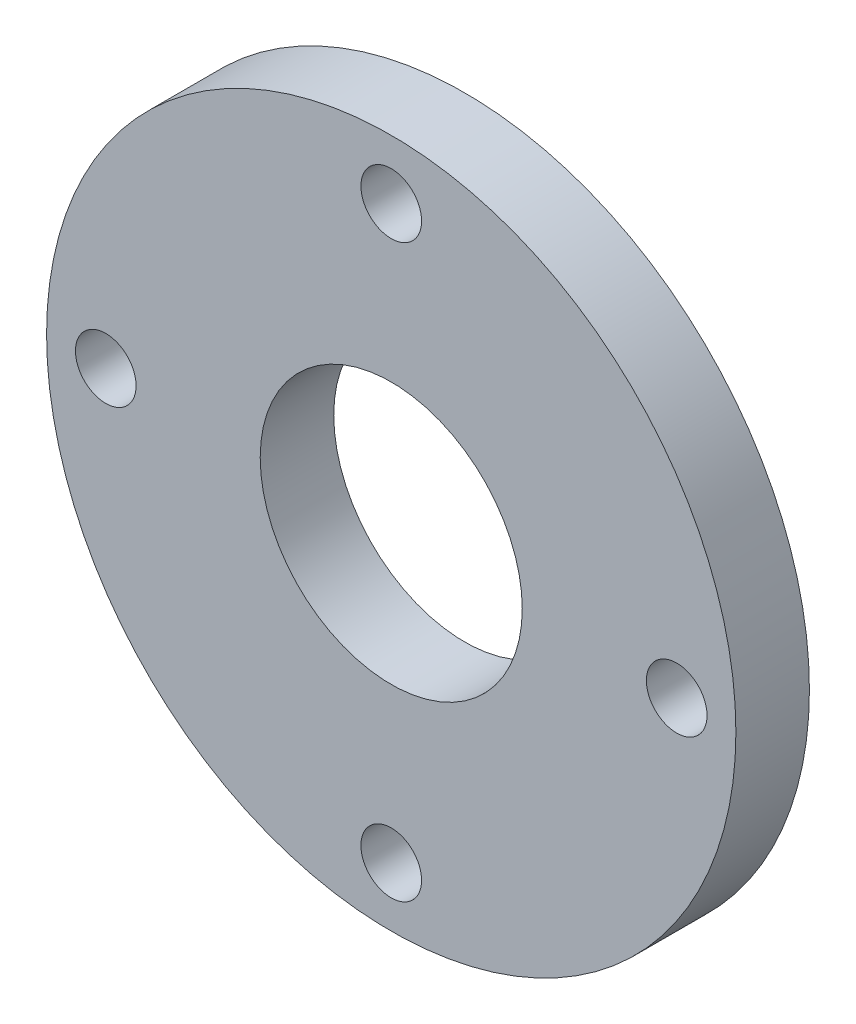
SolidWorks part; units mm, degrees
ref_plane "Front Plane" through (0, 0, 0) normal (0, 0, 1) x (1, 0, 0)
ref_plane "Top Plane" through (0, 0, 0) normal (0, 1, 0) x (1, 0, 0)
ref_plane "Right Plane" through (0, 0, 0) normal (1, 0, 0) x (0, 0, -1)
sketch "Sketch1" plane through (0, 0, 0) normal (1, 0, 0) x (0, 0, -1)
  line L0 (-108, -9.5) -> (-149, -9.5)
  line L5 (-1000, 0) -> (49000, 0)
  line L6 (0, -9.5) -> (0, 9.5)
  line L13 (0, 9.5) -> (-46.4, 9.5)
  line L26 (-46.4, 9.5) -> (-46.4, 14)
  line L27 (-46.4, 14) -> (-108, 14)
  line L32 (-108, 14) -> (-108, 9.5)
  line L34 (-165, 7) -> (-165, -7)
  line L36 (-108, -9.5) -> (-108, -14)
  line L37 (-108, -14) -> (-46.4, -14)
  line L38 (-46.4, -14) -> (-46.4, -9.5)
  line L39 (0, -9.5) -> (-46.4, -9.5)
  line L40 (-22.625, 37.5) -> (-14.625, 37.5)
  line L41 (-124.6, 22.6187) -> (-108, 22.6187)
  line L42 (-124.6, 22.6187) -> (-124.6, -22.6187)
  line L43 (-124.6, -22.6187) -> (-108, -22.6187)
  line L44 (-108, 22.6187) -> (-108, -22.6187)
  line L45 (-124.6, 22.6187) -> (-108, -22.6187) construction
  line L46 (-124.6, -22.6187) -> (-108, 22.6187) construction
  line L47 (-29.8, 22.6187) -> (-46.4, 22.6187)
  line L48 (-29.8, 22.6187) -> (-29.8, -22.6187)
  line L49 (-29.8, -22.6187) -> (-46.4, -22.6187)
  line L50 (-46.4, 22.6187) -> (-46.4, -22.6187)
  line L51 (-29.8, 22.6187) -> (-46.4, -22.6187) construction
  line L52 (-29.8, -22.6187) -> (-46.4, 22.6187) construction
  line L59 (-14.625, 37.5) -> (-14.625, -37.5)
  line L60 (-14.625, -37.5) -> (-22.625, -37.5)
  line L61 (-22.625, -22.6187) -> (-26.625, -22.6187)
  line L62 (-26.625, -22.6187) -> (-26.625, -12.5)
  line L63 (-26.625, -12.5) -> (-22.625, -12.5)
  line L64 (-22.625, -12.5) -> (-22.625, 12.5)
  line L65 (-22.625, 12.5) -> (-26.625, 12.5)
  line L66 (-26.625, 12.5) -> (-26.625, 22.6187)
  line L67 (-26.625, 22.6187) -> (-22.625, 22.6187)
  line L68 (-22.625, 22.6187) -> (-22.625, 37.5)
  line L69 (-22.625, -22.6187) -> (-22.625, -37.5)
  line L71 (-136.284, 37.5) -> (-23.625, 37.5)
  line L72 (-136.284, 37.5) -> (-136.284, -37.5)
  line L73 (-136.284, -37.5) -> (-23.625, -37.5)
  line L74 (-23.625, 37.5) -> (-23.625, -37.5)
  line L75 (-136.284, 37.5) -> (-23.625, -37.5) construction
  line L76 (-136.284, -37.5) -> (-23.625, 37.5) construction
  line L77 (-149, -9.5) -> (-149, -7)
  line L78 (-149, -7) -> (-165, -7)
  line L79 (-108, 9.5) -> (-149, 9.5)
  line L80 (-149, 7) -> (-165, 7)
  line L81 (-149, 9.5) -> (-149, 7)
  line L82 (-128.5, 9.5) -> (-128.5, -9.5) construction
  line L83 (-23.2, 9.5) -> (-23.2, -9.5) construction
  line L96 (-136.284, 37.5) -> (-144.284, 37.5)
  line L98 (-136.284, -37.5) -> (-144.284, -37.5)
  line L99 (-144.284, 37.5) -> (-144.284, -37.5)
  line L110 (-136.284, 37.5) -> (-136.284, -37.5)
  point P3 (0, 0)
  point P18 (-116.3, 0)
  point P24 (-38.1, 0)
  point P29 (-79.9545, 0)
  point P48 (-14.625, 31.0593)
  point P70 (-144.284, 31.0593)
revolve "Main_body" add sketch "Sketch1" angle 360 about L5 region at (0, 23.5, 140.284)
sketch "Sketch5" plane through (0, 0, 144.284) normal (0, 0, 1) x (1, 0, 0)
  circle A0 centre (0, 0) radius 14.2558
  dimension "D1" = 28.5115
extrude "seal_seat" cut sketch "Sketch5" against normal through all
hole_wizard "M6 Clearance Hole1" positions "Sketch3" profile "Sketch4" hole size "M6" standard "ANSI Metric" end condition through all
sketch "Sketch3" plane through (0, 0, 144.284) normal (0, 0, 1) x (1, 0, 0)
  point P0 (0, 31.0593)
sketch "Sketch4" plane through (0, 31.0593, 144.284) normal (1, 0, 0) x (0, -1, 0)
  line L0 (0, 0) -> (0, 8)
  line L1 (0, 8) -> (3.3, 8)
  line L2 (3.3, 8) -> (3.3, 0)
  line L5 (3.3, 0) -> (0, 0)
  line L11 (0, -6.35) -> (0, 107.95) construction
  dimension "Thru Hole Dia." = 6.6
  dimension "Thru Hole Depth" = 8
pattern_circular "CirPattern1" count 4 over 360 about axis through (0, 0, 1000) along (0, 0, -1) of "M6 Clearance Hole1"
